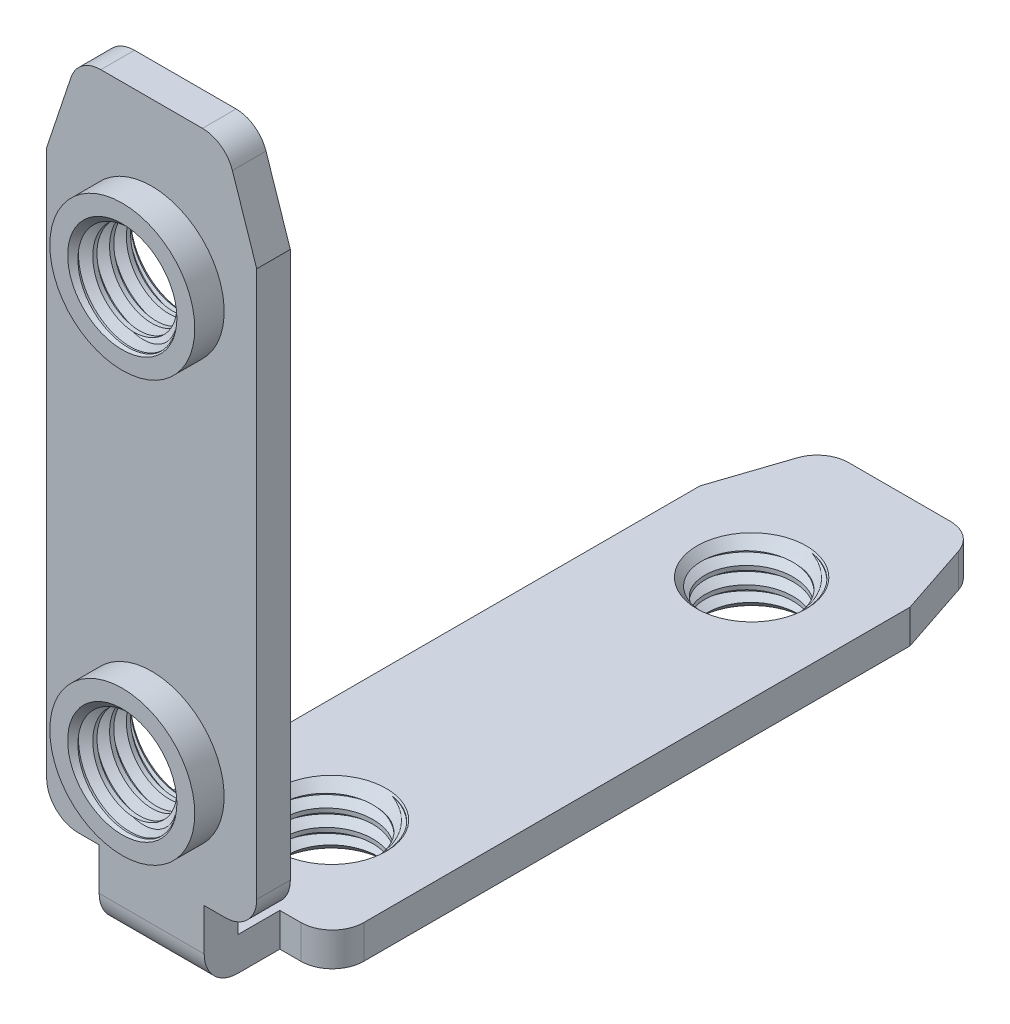
SolidWorks part; units mm, degrees
material "Plain Carbon Steel"
ref_plane "Front Plane" through (0, 0, 0) normal (0, 0, 1) x (1, 0, 0)
ref_plane "Top Plane" through (0, 0, 0) normal (0, 1, 0) x (1, 0, 0)
ref_plane "Right Plane" through (0, 0, 0) normal (1, 0, 0) x (0, 0, -1)
sketch "Sketch1" plane through (0, 0, 0) normal (0, 0, 1) x (1, 0, 0)
  line L0 (-10, 0) -> (0, 0) construction
  line L1 (0, 0) -> (0, 34) construction
  line L2 (-3.5, 2) -> (-2.5, 2)
  line L3 (-2.5, 2) -> (-2.5, 0)
  line L4 (-5, 3.5) -> (-5, 29.5)
  line L5 (-5, 29.5) -> (-3.8419, 32.9743)
  line L6 (-2.4189, 34) -> (2.4189, 34)
  line L7 (5, 29.5) -> (3.8419, 32.9743)
  line L8 (5, 3.5) -> (5, 29.5)
  line L9 (2.5, 2) -> (2.5, 0)
  line L10 (3.5, 2) -> (2.5, 2)
  line L11 (-2.5, 0) -> (2.5, 0)
  arc A0 (5, 3.5) -> (3.5, 2) centre (3.5, 3.5) cw
  arc A1 (-3.5, 2) -> (-5, 3.5) centre (-3.5, 3.5) cw
  arc A3 (-3.8419, 32.9743) -> (-2.4189, 34) centre (-2.4189, 32.5) cw
  arc A4 (3.8419, 32.9743) -> (2.4189, 34) centre (2.4189, 32.5) ccw
  point P16 (5, 2)
  point P19 (-5, 2)
  point P30 (-3.5, 34)
  point P33 (3.5, 34)
  dimension "D4" = 7
  dimension "D8" = 1.5
  dimension "D7" = 1.5
  dimension "D1" = 2
  dimension "D2" = 34
  dimension "D3" = 10
  dimension "D5" = 4.5
  dimension "D6" = 5
extrude "Boss-Extrude1" add sketch "Sketch1" along normal blind 1.6
sketch "Sketch2" plane through (0, 0, 1.6) normal (0, 0, 1) x (1, 0, 0)
  line L0 (-10, 0) -> (0, 0) construction
  line L2 (0, 0) -> (0, 34) construction
  line L3 (2.4189, 34) -> (-2.4189, 34) construction
  circle A0 centre (0, 6.96) radius 3.45
  circle A1 centre (0, 26.96) radius 3.45
  dimension "D1" = 6.9
  dimension "D3" = 6.96
  dimension "D2" = 20
extrude "Boss-Extrude2" add sketch "Sketch2" along normal blind 1.4
sketch "Sketch10" plane through (0, 0, 3) normal (0, 0, 1) x (1, 0, 0)
  circle A0 centre (0, 6.96) radius 2.1
  circle A1 centre (0, 26.96) radius 2.1
  circle A2 centre (0, 26.96) radius 3.45 construction
  circle A3 centre (0, 6.96) radius 3.45 construction
  dimension "D1" = 4.2
extrude "Cut-Extrude1" cut sketch "Sketch10" against normal through all
chamfer "Chamfer1" distance 0.5 angle 45 4 edges at (2.1, 6.96, 3) (2.1, 26.96, 3) (2.1, 6.96, 0) (2.1, 26.96, 0)
ref_plane "Plane1" through (0, 0, 0) normal (0, -0.7071, -0.7071) x (1, 0, 0)
sketch "Sketch5" plane through (2.5, 0, 0) normal (1, 0, 0) x (0, 0, -1)
  line L0 (0, 0) -> (-1.6, 0)
  line L1 (0, -1.6) -> (0, 0)
  arc A0 (-1.6, 0) -> (0, -1.6) centre (0, 0) ccw
extrude "Boss-Extrude3" add sketch "Sketch5" against normal up to surface (5 mm away) up to face at (-2.5, 1, 0.8)
mirror "Mirror4" about plane through (0, 0, 0) normal (0, -0.7071, -0.7071) of "Chamfer1", "Cut-Extrude1", "Boss-Extrude1", "Boss-Extrude2"
thread "Thread1" pitch 0.8 start angle 0, offset 1, length 5, pitch 0.8, diameter 4.2
ref_plane "Plane3" through (2.1, 26.96, -0.5) normal (0, -1, 0) x (1, 0, 0)
sketch "Thread Profile2" plane through (2.1, 26.96, -0.5) normal (0, -1, 0) x (1, 0, 0)
  line L0 (0, 0) -> (0, 0.8) construction
  line L1 (0, 0) -> (0.433, 0.25)
  line L2 (0.433, 0.25) -> (0.433, 0.35)
  line L3 (0.433, 0.35) -> (0, 0.6)
  line L4 (0.433, 0.3) -> (0, 0.3) construction
  line L11 (0, 0) -> (0, 0.6)
  point P2 (0, 0)
  dimension "Pitch" = 0.8
  dimension "Profile_Angle" = 60
  dimension "Profile_Land" = 0.1
  dimension "Profile_Height" = 0.433
thread "Thread2" pitch 0.8 profile "Thread Profile3" start angle 0, offset 1, length 5, pitch 0.8, diameter 4.2
ref_plane "Plane4" through (2.1, 6.96, -0.5) normal (0, -1, 0) x (1, 0, 0)
sketch "Thread Profile3" plane through (2.1, 6.96, -0.5) normal (0, -1, 0) x (1, 0, 0)
  line L0 (0, 0) -> (0, 0.8) construction
  line L1 (0, 0) -> (0.433, 0.25)
  line L2 (0.433, 0.25) -> (0.433, 0.35)
  line L3 (0.433, 0.35) -> (0, 0.6)
  line L4 (0.433, 0.3) -> (0, 0.3) construction
  line L11 (0, 0) -> (0, 0.6)
  point P2 (0, 0)
  dimension "Pitch" = 0.8
  dimension "Profile_Angle" = 60
  dimension "Profile_Land" = 0.1
  dimension "Profile_Height" = 0.433
thread "Thread3" pitch 0.8 profile "Thread Profile4" start angle 0, offset 1, length 5, pitch 0.8, diameter 4.2
ref_plane "Plane5" through (-2.1, 0.5, -6.96) normal (0, 0, 1) x (-1, 0, 0)
sketch "Thread Profile4" plane through (-2.1, 0.5, -6.96) normal (0, 0, 1) x (-1, 0, 0)
  line L0 (0, 0) -> (0, 0.8) construction
  line L1 (0, 0) -> (0.433, 0.25)
  line L2 (0.433, 0.25) -> (0.433, 0.35)
  line L3 (0.433, 0.35) -> (0, 0.6)
  line L4 (0.433, 0.3) -> (0, 0.3) construction
  line L11 (0, 0) -> (0, 0.6)
  point P2 (0, 0)
  dimension "Pitch" = 0.8
  dimension "Profile_Angle" = 60
  dimension "Profile_Land" = 0.1
  dimension "Profile_Height" = 0.433
thread "Thread4" pitch 0.8 profile "Thread Profile5" start angle 0, offset 1, length 5, pitch 0.8, diameter 4.2
ref_plane "Plane6" through (-2.1, 0.5, -26.96) normal (0, 0, 1) x (-1, 0, 0)
sketch "Thread Profile5" plane through (-2.1, 0.5, -26.96) normal (0, 0, 1) x (-1, 0, 0)
  line L0 (0, 0) -> (0, 0.8) construction
  line L1 (0, 0) -> (0.433, 0.25)
  line L2 (0.433, 0.25) -> (0.433, 0.35)
  line L3 (0.433, 0.35) -> (0, 0.6)
  line L4 (0.433, 0.3) -> (0, 0.3) construction
  line L11 (0, 0) -> (0, 0.6)
  point P2 (0, 0)
  dimension "Pitch" = 0.8
  dimension "Profile_Angle" = 60
  dimension "Profile_Land" = 0.1
  dimension "Profile_Height" = 0.433
